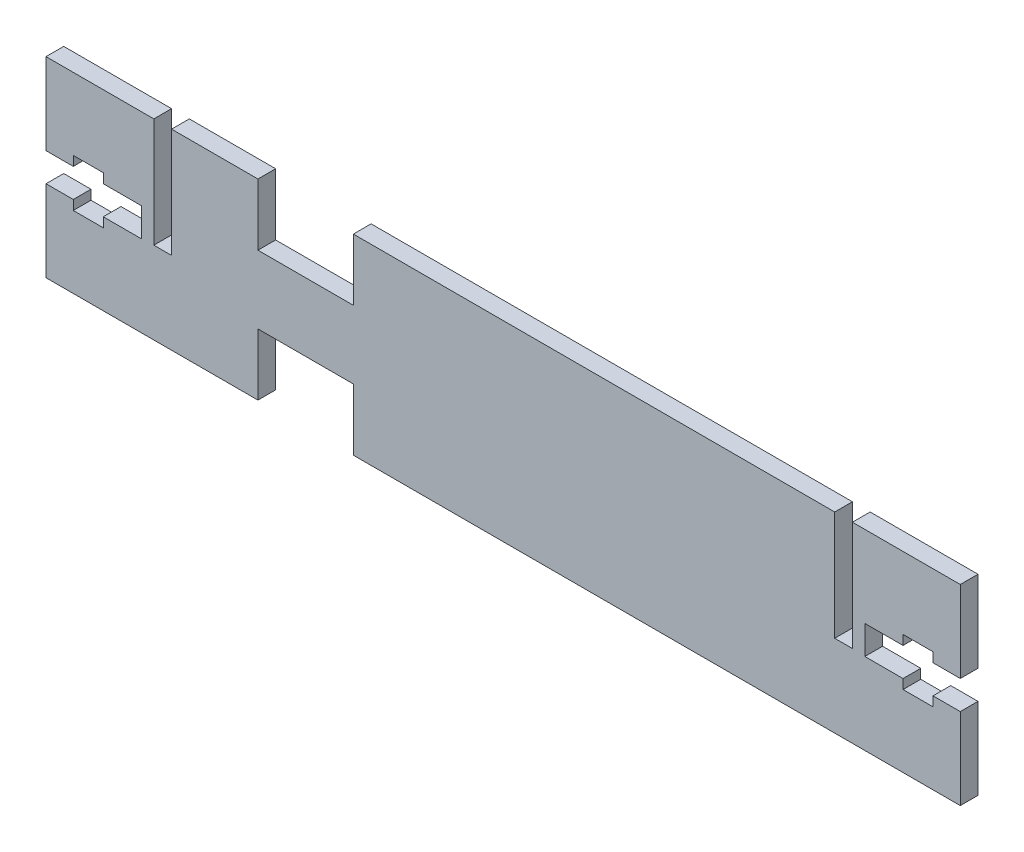
SolidWorks part; units mm, degrees
ref_plane "Front Plane" through (0, 0, 0) normal (0, 0, 1) x (1, 0, 0)
ref_plane "Top Plane" through (0, 0, 0) normal (0, 1, 0) x (1, 0, 0)
ref_plane "Right Plane" through (0, 0, 0) normal (1, 0, 0) x (0, 0, -1)
sketch "Sketch1" plane through (0, 0, 0) normal (0, 0, 1) x (1, 0, 0)
  line L0 (-63.4339, -2.54) -> (-63.4339, 17.8435) construction
  line L1 (85.1819, 17.8435) -> (-85.1819, 17.8435)
  line L2 (85.1819, 17.8435) -> (85.1819, -17.8435)
  line L3 (85.1819, -17.8435) -> (-85.1819, -17.8435)
  line L4 (-85.1819, 17.8435) -> (-85.1819, -17.8435)
  line L5 (85.1819, 17.8435) -> (-85.1819, -17.8435) construction
  line L6 (85.1819, -17.8435) -> (-85.1819, 17.8435) construction
  line L7 (-65.0849, 17.8435) -> (-61.7829, 17.8435)
  line L8 (-65.0849, 17.8435) -> (-65.0849, -2.54)
  line L9 (-65.0849, -2.54) -> (-61.7829, -2.54)
  line L10 (-61.7829, 17.8435) -> (-61.7829, -2.54)
  line L11 (0, 17.8435) -> (0, -17.8435) construction
  line L12 (63.4339, -2.54) -> (63.4339, 17.8435) construction
  line L13 (65.0849, 17.8435) -> (65.0849, -2.54)
  line L14 (65.0849, -2.54) -> (61.7829, -2.54)
  line L15 (61.7829, 17.8435) -> (61.7829, -2.54)
  point P0 (0, 0)
  dimension "D1" = 35.687
  dimension "D2" = 170.3639
  dimension "D3" = 21.748
  dimension "D4" = 3.302
  dimension "D5" = 2.54
extrude "Boss-Extrude1" add sketch "Sketch1" along normal mid plane 3.302 contours L15 L1 L10 L9 L8 L4 L3 L2 L13 L14 region at (0, -0.1733, 0)
sketch "Sketch2" plane through (0, 0, 1.651) normal (0, 0, 1) x (1, 0, 0)
  line L0 (-85.1819, 0) -> (85.1819, 0) construction
  line L1 (-85.1819, 17.8435) -> (-85.1819, -17.8435) construction
  line L2 (85.1819, 17.8435) -> (85.1819, -17.8435) construction
  line L3 (0, 17.8435) -> (0, -17.8435) construction
  line L4 (61.7829, 17.8435) -> (-61.7829, 17.8435) construction
  line L5 (85.1819, -17.8435) -> (-85.1819, -17.8435) construction
  line L6 (85.1819, 2.667) -> (80.1019, 2.667)
  line L7 (80.1019, 2.667) -> (80.1019, 4.445)
  line L8 (80.1019, 4.445) -> (74.5139, 4.445)
  line L9 (74.5139, 4.445) -> (74.5139, 2.667)
  line L10 (74.5139, 2.667) -> (67.4019, 2.667)
  line L11 (67.4019, 2.667) -> (67.4019, -2.667)
  line L12 (74.5139, -2.667) -> (67.4019, -2.667)
  line L13 (74.5139, -4.445) -> (74.5139, -2.667)
  line L14 (80.1019, -4.445) -> (74.5139, -4.445)
  line L15 (80.1019, -2.667) -> (80.1019, -4.445)
  line L16 (85.1819, -2.667) -> (80.1019, -2.667)
  line L17 (-85.1819, -2.667) -> (-80.1019, -2.667)
  line L18 (-80.1019, -2.667) -> (-80.1019, -4.445)
  line L19 (-80.1019, -4.445) -> (-74.5139, -4.445)
  line L20 (-74.5139, -4.445) -> (-74.5139, -2.667)
  line L21 (-74.5139, -2.667) -> (-67.4019, -2.667)
  line L22 (-67.4019, 2.667) -> (-67.4019, -2.667)
  line L23 (-74.5139, 2.667) -> (-67.4019, 2.667)
  line L24 (-74.5139, 4.445) -> (-74.5139, 2.667)
  line L25 (-80.1019, 4.445) -> (-74.5139, 4.445)
  line L26 (-80.1019, 2.667) -> (-80.1019, 4.445)
  line L27 (-85.1819, 2.667) -> (-80.1019, 2.667)
  line L28 (85.1819, 2.667) -> (85.1819, -2.667)
  line L29 (-85.1819, 2.667) -> (-85.1819, -2.667)
  point P20 (67.4019, 0)
  point P37 (-67.4019, 0)
  dimension "D1" = 5.08
  dimension "D2" = 4.445
  dimension "D3" = 2.667
  dimension "D4" = 5.588
  dimension "D5" = 17.78
extrude "Cut-Extrude1" cut sketch "Sketch2" against normal through all
sketch "Sketch3" plane through (0, 0, 1.651) normal (0, 0, 1) x (1, 0, 0)
  line L1 (-27.9116, 6.35) -> (-45.6916, 6.35)
  line L2 (-27.9116, 6.35) -> (-27.9116, -6.35)
  line L3 (-27.9116, -6.35) -> (-45.6916, -6.35)
  line L4 (-45.6916, 6.35) -> (-45.6916, -6.35)
  line L5 (-27.9116, 6.35) -> (-45.6916, -6.35) construction
  line L6 (-27.9116, -6.35) -> (-45.6916, 6.35) construction
  line L8 (-43.1516, -8.89) -> (-30.4516, -8.89) construction
  line L9 (-27.9116, -6.35) -> (-27.9116, -17.8435)
  line L10 (85.1819, -17.8435) -> (-85.1819, -17.8435) construction
  line L11 (-27.9116, -17.8435) -> (-45.6916, -17.8435)
  line L12 (-45.6916, -17.8435) -> (-45.6916, -6.35)
  line L13 (0, 0) -> (-45.6916, 0) construction
  line L14 (-45.6916, 17.8435) -> (-45.6916, 6.35)
  line L15 (-27.9116, 17.8435) -> (-45.6916, 17.8435)
  line L16 (-27.9116, 6.35) -> (-27.9116, 17.8435)
  line L17 (-30.4516, 13.8345) -> (-30.4516, -3.3461) construction
  line L18 (-43.1516, -3.3461) -> (-43.1516, 13.8345) construction
  point P0 (-36.8016, 0)
  line M17 (-85.1819, -17.8435) -> (85.1819, -17.8435)
  line M35 (61.7829, 17.8435) -> (-61.7829, 17.8435)
  dimension "D1" = 2.54
  dimension "D2" = 2.54
  dimension "D3" = 2.54
extrude "Cut-Extrude2" cut sketch "Sketch3" against normal blind 12.192 contours L12 L9 L3 M17 | L1 L16 L14 M35 region at (-36.8016, 12.0967, 1.651) region at (-36.8016, -12.0967, 1.651)
